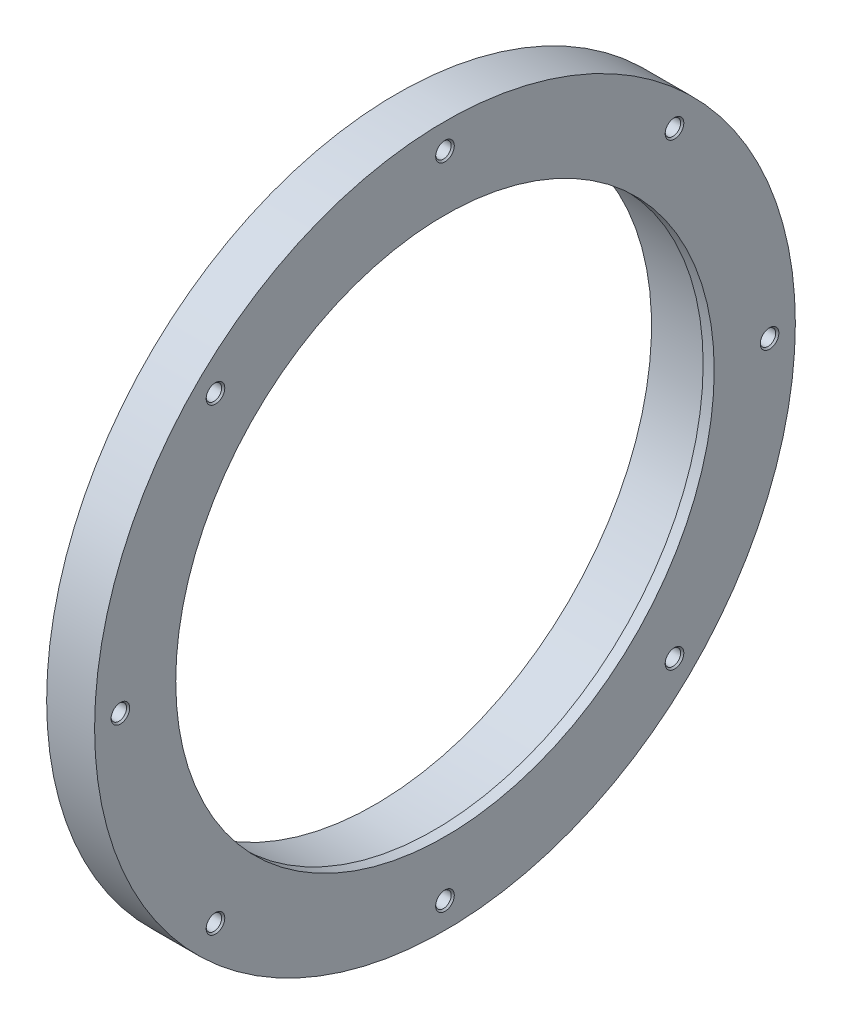
SolidWorks part; units mm, degrees
material "Stop 1060"
ref_plane "Płaszczyzna przednia" through (0, 0, 0) normal (0, 0, 1) x (1, 0, 0)
ref_plane "Płaszczyzna górna" through (0, 0, 0) normal (0, 1, 0) x (1, 0, 0)
ref_plane "Płaszczyzna prawa" through (0, 0, 0) normal (1, 0, 0) x (0, 0, -1)
sketch "Szkic1" plane through (0, 0, 0) normal (0, 0, 1) x (1, 0, 0)
  line L0 (0, 0) -> (67.9681, 0) construction
  line L16 (19, 95) -> (6, 95)
  line L17 (6, 80) -> (0, 80)
  line L18 (16, 75) -> (0, 75)
  line L19 (16, 73) -> (19, 73)
  line L20 (16, 73) -> (16, 75)
  line L21 (19, 95) -> (19, 73)
  line L22 (0, 80) -> (0, 75)
  line L23 (6, 80) -> (6, 95)
revolve "Obrót1" add sketch "Szkic1" angle 360 about L0
hole_wizard "Otwór gwintowany M51" positions "Szkic3" profile "Szkic5" tap size "M5" standard "DIN" end condition through all
sketch "Szkic3" plane through (19, 0, 0) normal (1, 0, 0) x (0, 0, -1)
  point P0 (0, 88)
  point P12 (62.2254, 62.2254)
  point P13 (88, 0)
  point P14 (62.2254, -62.2254)
  point P15 (0, -88)
  point P16 (-62.2254, -62.2254)
  point P17 (-88, 0)
  point P18 (-62.2254, 62.2254)
  point P19 (0, 0)
  dimension "D1" = 88
  dimension "D2" = 8
sketch "Szkic5" plane through (19, 88, 0) normal (0, 1, 0) x (0, 0, -1)
  line L0 (0, 0) -> (0, 19)
  line L1 (0, 19) -> (2.1, 19)
  line L2 (2.1, 19) -> (2.1, 0.425)
  line L3 (2.1, 0.425) -> (2.525, 0)
  line L5 (2.525, 0) -> (0, 0)
  line L6 (-2.1, 0.425) -> (-2.525, 0) construction
  line L11 (0, -6.35) -> (0, 107.95) construction
  dimension "Średnica otworu gwintowanego na wylot" = 4.2
  dimension "Głębokość otworu gwintowanego na wylot" = 19
  dimension "Średnica zewnętrznego pogłębienia stożkowego" = 5.05
  dimension "Kąt zewnętrznego pogłębienia stożkowego" = 90
cosmetic thread "Gwint otworu1"
cosmetic thread "Gwint otworu2"
cosmetic thread "Gwint otworu3"
cosmetic thread "Gwint otworu4"
cosmetic thread "Gwint otworu5"
cosmetic thread "Gwint otworu6"
cosmetic thread "Gwint otworu7"
cosmetic thread "Gwint otworu8"
